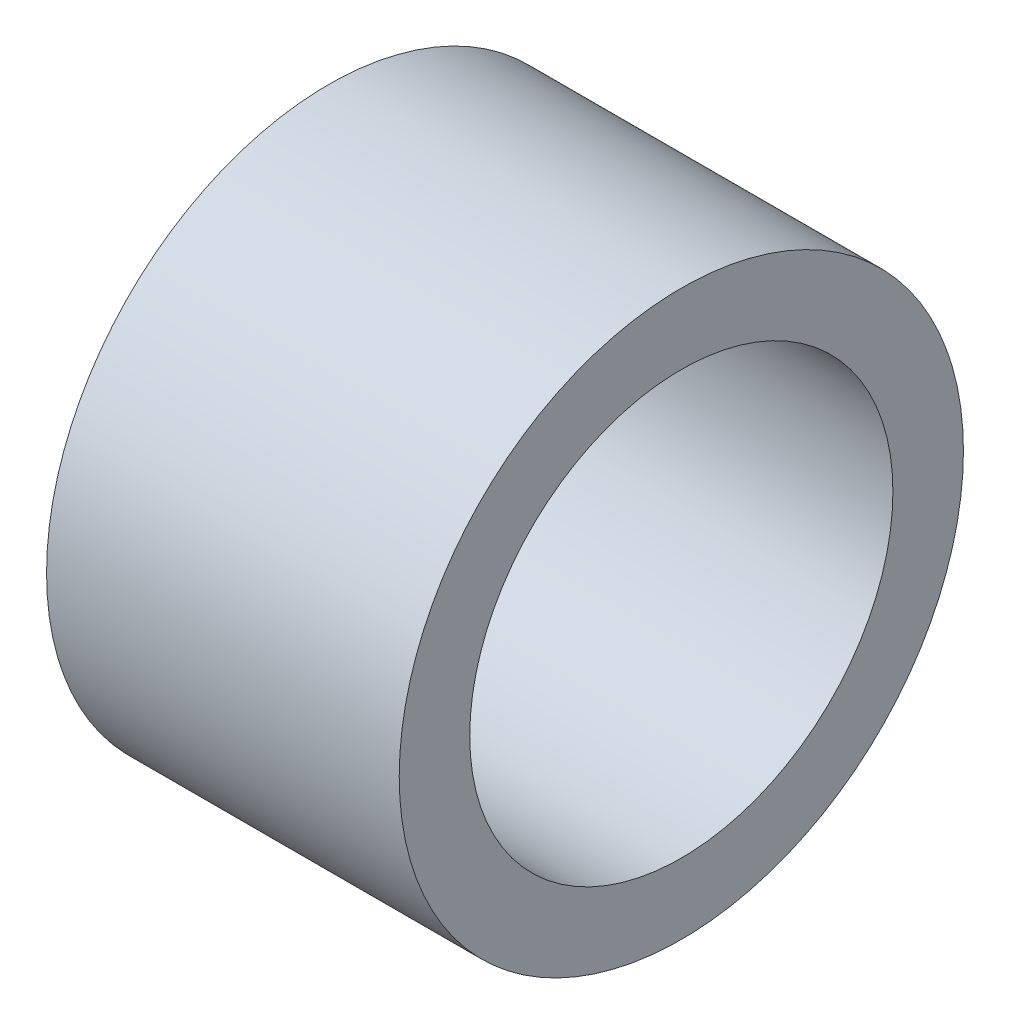
SolidWorks part; units mm, degrees
material "Plain Carbon Steel"
ref_plane "Plane1" through (0, 0, 0) normal (0, 0, 1) x (1, 0, 0)
ref_plane "Plane2" through (0, 0, 0) normal (0, 1, 0) x (1, 0, 0)
ref_plane "Plane3" through (0, 0, 0) normal (1, 0, 0) x (0, 0, -1)
sketch "Clipboard" plane through (0, 0, 0) normal (0, 0, 1) x (1, 0, 0)
  line L0 (-10, 0) -> (10, 0) construction
  line L1 (5, 0.1746) -> (27.3471, -0.6058)
  line L2 (5, 0.1746) -> (36.9805, 1.2914)
  line L3 (5, 0.1746) -> (19.25, -0.323)
  line L4 (5, 0.1746) -> (-20, -0.6984)
  dimension "OD" = 32
  dimension "Count" = 2
  dimension "Show_count" = 2
  dimension "Max_count" = 2
  dimension "Min_count" = 2
  dimension "RollCLRad" = 14.25
  dimension "Bore" = 25
sketch "CagSpiSke" plane through (0, 0, 0) normal (0, 0, 1) x (1, 0, 0)
  line L0 (8, 13.9) -> (8, 14.6)
  line L1 (8, 14.6) -> (-8, 14.6)
  line L2 (-8, 14.6) -> (-8, 13.9)
  line L3 (-8, 13.9) -> (8, 13.9)
  line L4 (-12.7, 0) -> (12.7, 0) construction
  dimension "cagRadius" = 13.9
  dimension "thickness" = 0.7
  dimension "Width" = 16
  dimension "halfWidth" = 8
revolve "CageSpine" add sketch "CagSpiSke" angle 360 about L4 reverse direction yes
sketch "RolDetSke" plane through (0, 0, 0) normal (0, 0, 1) x (1, 0, 0)
  line L0 (-17.78, 14.25) -> (17.78, 14.25) construction
  line L2 (-7.13, 16) -> (7.13, 16)
  line L3 (-7.2, 15.93) -> (-7.2, 14.25)
  line L5 (-7.2, 14.25) -> (7.2, 14.25)
  line L6 (7.2, 15.93) -> (7.2, 14.25)
  arc A0 (-7.13, 16) -> (-7.2, 15.93) centre (-7.13, 15.93) ccw
  arc A1 (7.2, 15.93) -> (7.13, 16) centre (7.13, 15.93) ccw
  dimension "radius" = 0.07
  dimension "CLRad" = 14.25
  dimension "Cyl_Len" = 14.4
  dimension "halfCylLen" = 7.2
  dimension "Roller_diameter" = 3.5
revolve "RollerDetailed" [suppressed] add sketch "RolDetSke" angle 360 about L0 reverse direction yes
ref_axis "Axis1" through (-50, 0, 0) along (1, 0, 0)
pattern_circular "RollersDetailed" [suppressed] count 2 every 180 about axis through (-50, 0, 0) along (1, 0, 0)
sketch "RolSimSke" plane through (0, 0, 0) normal (0, 0, 1) x (1, 0, 0)
  line L0 (-17.78, 0) -> (17.78, 0) construction
  line L1 (-12.7, 0) -> (-38.1, 0) construction
  line L3 (-7.13, 16) -> (7.13, 16)
  line L4 (-7.2, 15.93) -> (-7.2, 12.57)
  line L5 (-7.13, 12.5) -> (7.13, 12.5)
  line L6 (7.2, 15.93) -> (7.2, 12.57)
  arc A0 (7.2, 12.57) -> (7.13, 12.5) centre (7.13, 12.57) cw
  arc A1 (7.13, 16) -> (7.2, 15.93) centre (7.13, 15.93) cw
  arc A2 (-7.2, 15.93) -> (-7.13, 16) centre (-7.13, 15.93) cw
  arc A3 (-7.13, 12.5) -> (-7.2, 12.57) centre (-7.13, 12.57) cw
  point P13 (7.2, 16)
  point P16 (-7.2, 16)
  point P19 (-7.2, 12.5)
  dimension "Bore" = 25
  dimension "radius" = 0.07
  dimension "Cyl_Len" = 14.4
  dimension "Roller_diameter" = 3.5
  dimension "D1" = 7.2
revolve "RollersSimplified" add sketch "RolSimSke" angle 360 about L0
sketch "Sketch1" plane through (0, 0, 0) normal (1, 0, 0) x (0, 0, -1)
  circle A3 centre (0, 0) radius 12
  circle A4 centre (0, 0) radius 16 construction
  circle A5 centre (0, 0) radius 16
  dimension "D1" = 24
extrude "Boss-Extrude1" add sketch "Sketch1" along normal mid plane 20
equation "\"RollCLRad@Clipboard\" = ( \"OD@Clipboard\" + \"Bore@Clipboard\" )  / 4"
equation "\"CLRad@RolDetSke\" = \"RollCLRad@Clipboard\""
equation "\"thickness@CagSpiSke\"  = ( \"OD@Clipboard\" - \"Bore@Clipboard\" )  / 10"
equation "\"cagRadius@CagSpiSke\" =  \"RollCLRad@Clipboard\" -  ( \"thickness@CagSpiSke\" / 2 ) "
equation "\"halfWidth@CagSpiSke\" = \"Width@CagSpiSke\" / 2"
equation "\"Bore@RolSimSke\" = \"Bore@Clipboard\""
equation "\"Roller_diameter@RolDetSke\" =  ( \"OD@Clipboard\" - \"Bore@Clipboard\" )  / 2"
equation "\"halfCylLen@RolDetSke\" = \"Cyl_Len@RolDetSke\" / 2"
equation "\"radius@RolDetSke\" = \"Roller_diameter@RolDetSke\" / 50"
equation "\"Cyl_Len@RolSimSke\" = \"Cyl_Len@RolDetSke\""
equation "\"D1@RolSimSke\" = \"Cyl_Len@RolSimSke\"/2"
equation "\"radius@RolSimSke\" = \"radius@RolDetSke\""
equation "\"Roller_diameter@RolSimSke\" =  ( \"OD@Clipboard\" - \"Bore@Clipboard\" )  / 2"
equation "\"Max_count@Clipboard\" = int( 3.14159265 / atn(( \"Roller_diameter@RolDetSke\" / 2) / sqr(\"RollCLRad@Clipboard\"  * \"RollCLRad@Clipboard\" - ( \"Roller_diameter@RolDetSke\" / 2) *  ( \"Roller_diameter@RolDetSke\" / 2))))"
equation "\"Max_count@Clipboard\" = ((sgn( \"Max_count@Clipboard\" - \"Count@Clipboard\" )-1)*( \"Max_count@Clipboard\" - \"Count@Clipboard\" ))/-2+ \"Count@Clipboard\""
equation "\"Count@RollersDetailed\" = int( \"Show_count@Clipboard\" ) "
equation "\"Count@RollersDetailed\" = ((sgn( \"Count@RollersDetailed\" - \"Max_count@Clipboard\" )-1)*( \"Count@RollersDetailed\" - \"Max_count@Clipboard\" ))/-2+ \"Max_count@Clipboard\""
equation "\"Count@RollersDetailed\" = ((sgn( \"Count@RollersDetailed\" - \"Min_count@Clipboard\" )+1)*( \"Count@RollersDetailed\" - \"Min_count@Clipboard\"))/2 +\"Min_count@Clipboard\""
equation "\"Angle@RollersDetailed\" = 360.0 / \"Max_count@Clipboard\""
